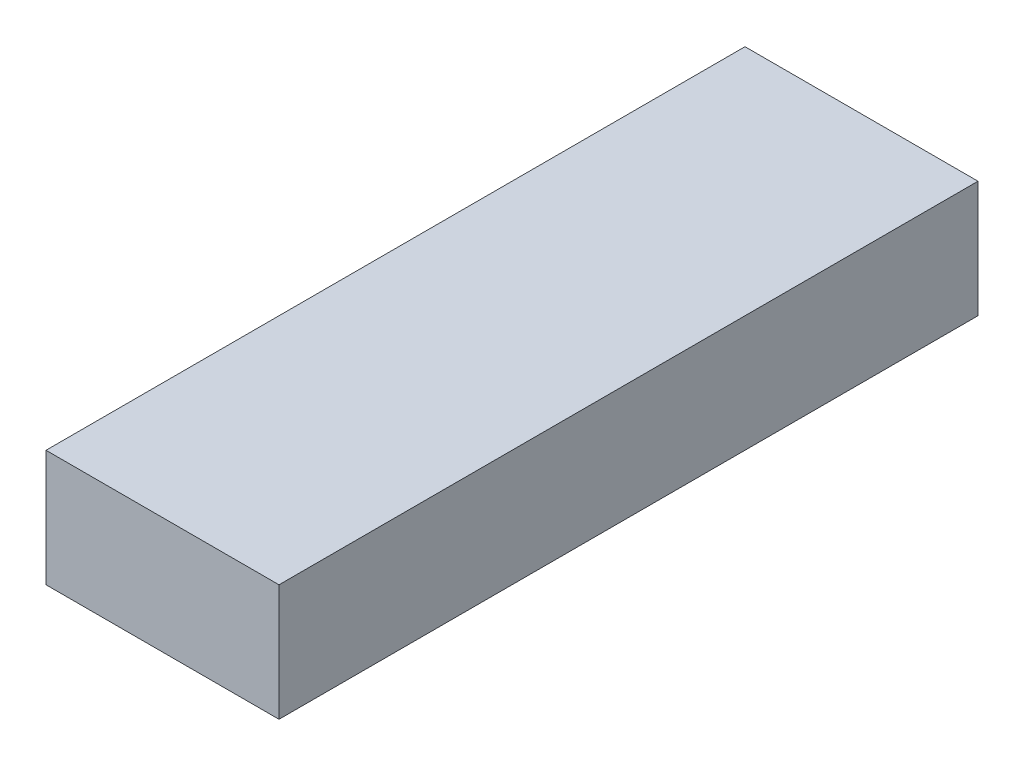
SolidWorks part; units mm, degrees
ref_plane "Front Plane" through (0, 0, 0) normal (0, 0, 1) x (1, 0, 0)
ref_plane "Top Plane" through (0, 0, 0) normal (0, 1, 0) x (1, 0, 0)
ref_plane "Right Plane" through (0, 0, 0) normal (1, 0, 0) x (0, 0, -1)
sketch "Sketch1" plane through (0, 0, 0) normal (0, 0, 1) x (1, 0, 0)
  line L1 (-25.4, -12.7) -> (25.4, -12.7)
  line L2 (-25.4, -12.7) -> (-25.4, 12.7)
  line L3 (-25.4, 12.7) -> (25.4, 12.7)
  line L4 (25.4, -12.7) -> (25.4, 12.7)
  line L5 (-25.4, -12.7) -> (25.4, 12.7) construction
  line L6 (-25.4, 12.7) -> (25.4, -12.7) construction
  point P0 (0, 0)
  dimension "D1" = 25.4
  dimension "D2" = 50.8
extrude "Boss-Extrude1" add sketch "Sketch1" along normal blind 152.4
